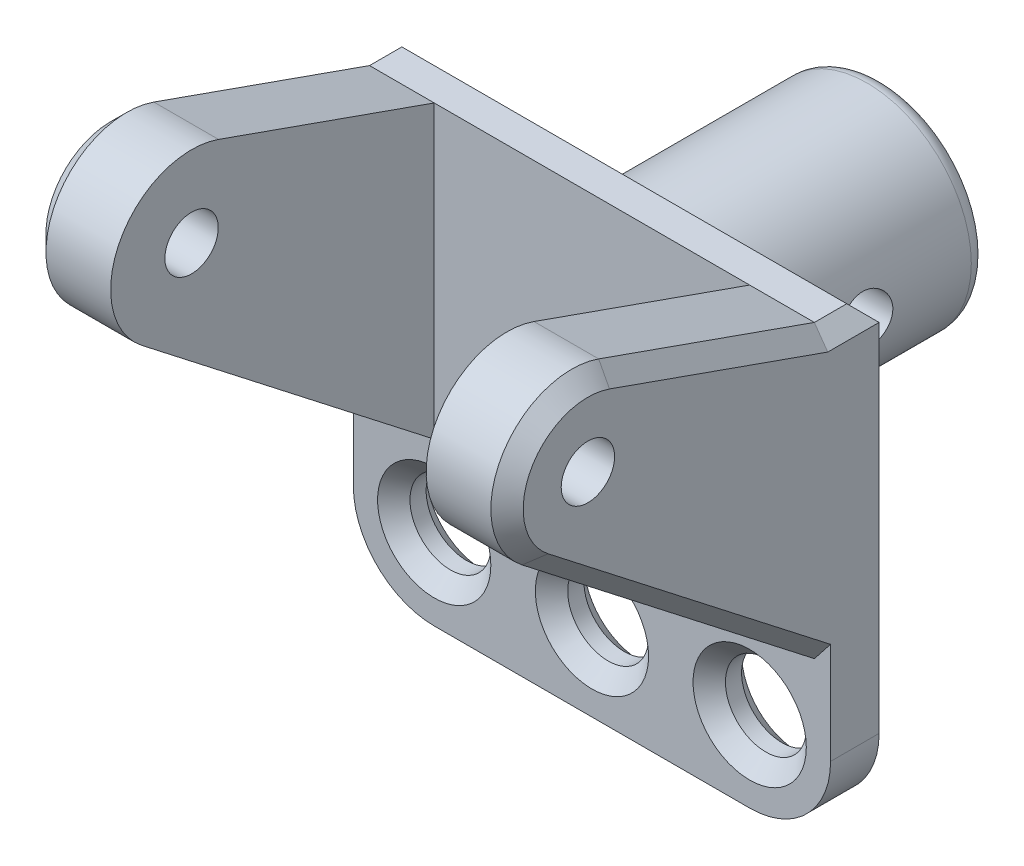
SolidWorks part; units mm, degrees
ref_plane "正面(Front)" through (0, 0, 0) normal (0, 0, 1) x (1, 0, 0)
ref_plane "平面(Top)" through (0, 0, 0) normal (0, 1, 0) x (1, 0, 0)
ref_plane "右側面(Right)" through (0, 0, 0) normal (1, 0, 0) x (0, 0, -1)
sketch "ｽｹｯﾁ1" plane through (0, 0, 0) normal (0, 0, 1) x (1, 0, 0)
  circle A0 centre (0, 0) radius 6.45
  dimension "D1" = 12.9
extrude "ﾎﾞｽ - 押し出し1" add sketch "ｽｹｯﾁ1" along normal blind 15
sketch "ｽｹｯﾁ2" plane through (0, 0, 15) normal (0, 0, 1) x (1, 0, 0)
  line L1 (-14.75, 9) -> (14.75, 9)
  line L2 (-14.75, 9) -> (-14.75, -9)
  line L3 (-14.75, -9) -> (14.75, -9)
  line L4 (14.75, 9) -> (14.75, -9)
  line L5 (-14.75, 9) -> (14.75, -9) construction
  line L6 (-14.75, -9) -> (14.75, 9) construction
  point P0 (0, 0)
  dimension "D1" = 18
  dimension "D2" = 29.5
extrude "ﾎﾞｽ - 押し出し2" add sketch "ｽｹｯﾁ2" along normal blind 3
sketch "ｽｹｯﾁ3" plane through (0, 0, 0) normal (1, 0, 0) x (0, 0, -1)
  line L0 (-18, 9) -> (-31.3333, 13.714)
  line L1 (-36.0696, 5.0531) -> (-18, -9)
  line L2 (-18, 9) -> (-42.4502, 9) construction
  line L4 (-18, 9) -> (-18, -9)
  arc A0 (-31.3333, 13.714) -> (-36.0696, 5.0531) centre (-33, 9) ccw
  circle A1 centre (-33, 9) radius 1.65
  dimension "D2" = 5
  dimension "D3" = 3.3
  dimension "D1" = 15
extrude "ﾎﾞｽ - 押し出し3" add sketch "ｽｹｯﾁ3" against normal blind 5 from surface starting at face at (14.75, 0, 16.5)
extrude "ﾎﾞｽ - 押し出し4" add sketch "ｽｹｯﾁ3<2>" along normal blind 5 from surface starting at face at (-14.75, 0, 16.5)
sketch "ｽｹｯﾁ3<2>" plane through (0, 0, 0) normal (1, 0, 0) x (0, 0, -1) same geometry as "ｽｹｯﾁ3"
sketch "ｽｹｯﾁ4" plane through (0, -9, 0) normal (0, -1, 0) x (1, 0, 0)
  line L6 (-14.75, 15) -> (14.75, 15)
  line L7 (14.75, 15) -> (14.75, 18)
  line L8 (14.75, 18) -> (9.75, 18)
  line L9 (9.75, 18) -> (-9.75, 18)
  line L10 (-9.75, 18) -> (-14.75, 18)
  line L11 (-14.75, 18) -> (-14.75, 15)
  line L12 (-14.75, 15) -> (14.75, 15)
  line L13 (14.75, 15) -> (14.75, 18)
  line L14 (14.75, 18) -> (9.75, 18)
  line L15 (9.75, 18) -> (-9.75, 18)
  line L16 (-9.75, 18) -> (-14.75, 18)
  line L17 (-14.75, 18) -> (-14.75, 15)
  dimension "D1" = 0
extrude "ﾎﾞｽ - 押し出し5" add sketch "ｽｹｯﾁ4" along normal blind 10
fillet "ﾌｨﾚｯﾄ1" radius 5 2 edges at (-14.75, -19, 16.5) (14.75, -19, 16.5)
sketch "ｽｹｯﾁ5" plane through (0, 0, 18) normal (0, 0, 1) x (1, 0, 0)
  line L0 (0, 0) -> (0, -31.2468) construction
  line L1 (9.75, -9) -> (14.75, -9) construction
  line L2 (-9.75, 5.0531) -> (-9.75, -9) construction
  circle A0 centre (0, -14) radius 2.5
  circle A1 centre (-9.75, -14) radius 2.5
  circle A2 centre (9.75, -14) radius 2.5
  dimension "D1" = 5
  dimension "D2" = 5
  dimension "D3" = 5
extrude "ｶｯﾄ - 押し出し1" cut sketch "ｽｹｯﾁ5" against normal through all
chamfer "面取り1" distance 1 angle 45 6 edges at (12.25, -14, 15) (2.5, -14, 15) (-7.25, -14, 15) (-7.25, -14, 18) (2.5, -14, 18) (7.25, -14, 18)
chamfer "面取り2" distance 1 angle 45 9 edges at (-14.75, 9, 16.5) (0, 9, 15) (14.75, 9, 16.5) (-14.75, 11.357, 24.6667) (-14.75, 11.399, 37.3869) (-14.75, -1.9734, 27.0348) (14.75, 11.357, 24.6667) (14.75, 11.399, 37.3869) (14.75, -1.9734, 27.0348)
sketch "ｽｹｯﾁ6" plane through (0, 0, 0) normal (1, 0, 0) x (0, 0, -1)
  line L0 (0, 0) -> (-31.3812, 0) construction
  line L1 (0, -6.45) -> (0, 6.45) construction
  line L2 (-8.9289, -0.825) -> (-9.4053, 0)
  line L3 (-9.4053, 0) -> (-8.9289, 0.825)
  arc A0 (-8.9289, -0.825) -> (-8.9289, 0.825) centre (-7.5, 0) ccw
  dimension "D1" = 3.3
  dimension "D2" = 7.5
  dimension "D3" = 60
extrude "ｶｯﾄ - 押し出し2" cut sketch "ｽｹｯﾁ6" against normal through all both and the other way through all
fillet "ﾌｨﾚｯﾄ2" radius 1 1 edges at (6.45, 0, 0)
